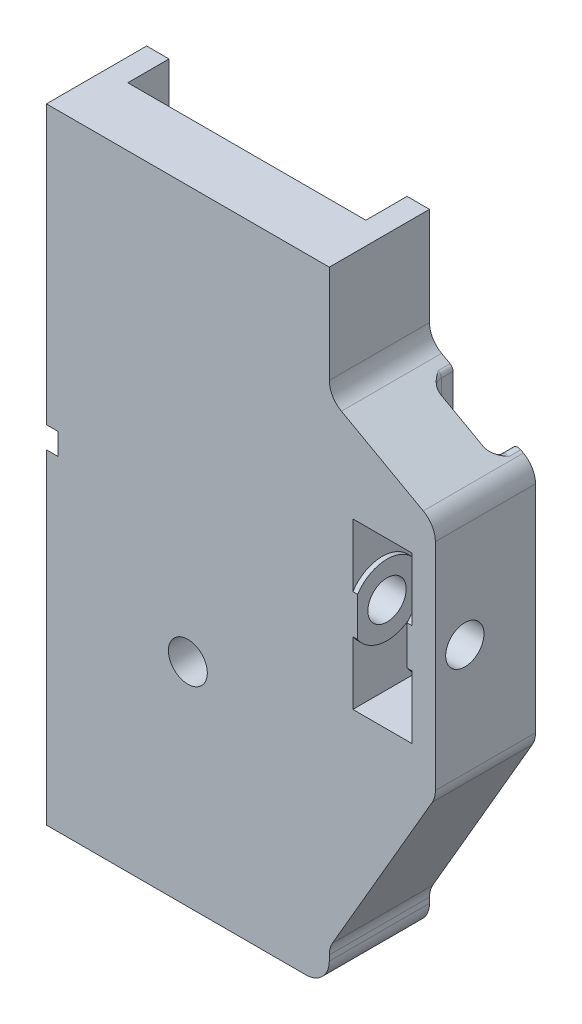
SolidWorks part; units mm, degrees
material "ABS"
ref_plane "前视基准面" through (0, 0, 0) normal (0, 0, 1) x (1, 0, 0)
ref_plane "上视基准面" through (0, 0, 0) normal (0, 1, 0) x (1, 0, 0)
ref_plane "右视基准面" through (0, 0, 0) normal (1, 0, 0) x (0, 0, -1)
other "Configuration Table"
sketch "草图1" plane through (0, 0, 0) normal (0, 0, 1) x (1, 0, 0)
  line L0 (0, 0) -> (0, 53)
  line L1 (0, 53) -> (24, 53)
  line L2 (24, 53) -> (24, 43.5)
  line L3 (24, 43.5) -> (33, 38.5)
  line L4 (33, 38.5) -> (33, 18.5)
  line L5 (33, 18.5) -> (24, 3)
  line L6 (24, 3) -> (24, 0)
  line L7 (24, 0) -> (0, 0)
  line L9 (26, 35.5) -> (31, 35.5)
  line L10 (26, 35.5) -> (26, 21.5)
  line L11 (26, 21.5) -> (31, 21.5)
  line L12 (31, 35.5) -> (31, 21.5)
  circle A0 centre (12, 18) radius 1.65
  dimension "D12" = 3.3
  dimension "D13" = 12
  dimension "D14" = 18
  dimension "D1" = 53
  dimension "D2" = 24
  dimension "D3" = 9
  dimension "D4" = 3
  dimension "D5" = 20
  dimension "D6" = 5
  dimension "D7" = 14.5
  dimension "D8" = 5
  dimension "D9" = 14
  dimension "D10" = 2
  dimension "D11" = 3
extrude "凸台-拉伸1" add sketch "草图1" along normal blind 8.5
sketch "草图2" plane through (0, 53, 0) normal (0, 1, 0) x (1, 0, 0)
  line L0 (24, 0) -> (0, 0) construction
  line L1 (1.9, 0) -> (22.1, 0)
  line L2 (1.9, 0) -> (1.9, -3.5)
  line L3 (1.9, -3.5) -> (22.1, -3.5)
  line L4 (22.1, 0) -> (22.1, -3.5)
  line L5 (0, -8.5) -> (0, 0) construction
  dimension "D1" = 3.5
  dimension "D2" = 1.9
  dimension "D3" = 20.2
extrude "切除-拉伸1" cut sketch "草图2" against normal offset from surface (50.1 mm away) 2.9 up to face at (12, 0, 4.25)
sketch "草图3" plane through (33, 0, 0) normal (1, 0, 0) x (0, 0, -1)
  line L0 (-8.5, 18.5) -> (-8.5, 38.5) construction
  circle A0 centre (-6, 28.5) radius 1.625
  dimension "D1" = 3.25
  dimension "D2" = 2.5
  dimension "D3" = 7
extrude "切除-拉伸2" cut sketch "草图3" against normal up to surface (7 mm away) up to face at (26, 28.5, 4.25)
sketch "草图4" plane through (26, 0, 0) normal (1, 0, 0) x (0, 0, -1)
  circle A0 centre (-6, 28.5) radius 1
  dimension "D1" = 2
extrude "切除-拉伸3" cut sketch "草图4" against normal up to surface (3.9 mm away) up to face at (22.1, 27.95, 1.75)
sketch "草图5" plane through (26, 0, 0) normal (1, 0, 0) x (0, 0, -1)
  line L0 (-8.5, 35.5) -> (-8.5, 21.5) construction
  line L1 (-8.5, 30.1583) -> (-8.5, 26.8417)
  circle A0 centre (-6, 28.5) radius 1 construction
  circle A1 centre (-6, 28.5) radius 1
  arc A2 (-8.5, 26.8417) -> (-8.5, 30.1583) centre (-6, 28.5) ccw
  dimension "D1" = 6
extrude "凸台-拉伸2" add sketch "草图5" along normal blind 0.4
sketch "草图6" plane through (31, 0, 0) normal (-1, 0, 0) x (0, 0, 1)
  line L1 (8.5, 26.8417) -> (8.5, 30.1583)
  line L2 (8.5, 26.8417) -> (8.5, 30.1583)
  circle A0 centre (6, 28.5) radius 1.625 construction
  arc A1 (8.5, 30.1583) -> (8.5, 26.8417) centre (6, 28.5) ccw
  arc A2 (8.5, 30.1583) -> (8.5, 26.8417) centre (6, 28.5) ccw
  circle A3 centre (6, 28.5) radius 1.625
  dimension "D1" = 0
extrude "凸台-拉伸3" add sketch "草图6" along normal blind 0.4
fillet "圆角1" radius 2 1 edges at (24, 3, 4.25)
fillet "圆角2" radius 2 4 edges at (24, 0, 4.25) (33, 18.5, 4.25) (33, 38.5, 4.25) (24, 43.5, 4.25)
sketch "草图7" plane through (33, 0, 0) normal (1, 0, 0) x (0, 0, -1)
  circle A0 centre (-6, 28.5) radius 1.625 construction
  circle A1 centre (-6, 28.5) radius 1.625
extrude "切除-拉伸4" cut sketch "草图7" against normal through all
sketch "草图8" plane through (0, 0, 0) normal (0, 0, -1) x (-1, 0, 0)
  line L0 (-26, 35.5) -> (-26, 21.5) construction
  line L1 (-31, 35.5) -> (-26, 35.5)
  line L2 (-31, 35.5) -> (-31, 44.8225)
  line L3 (-31, 44.8225) -> (-26, 44.8225)
  line L4 (-26, 35.5) -> (-26, 44.8225)
extrude "切除-拉伸5" cut sketch "草图8" against normal blind 2
fillet "圆角3" radius 0.5 2 edges at (31, 39.6111, 1) (26, 42.3889, 1)
fillet "圆角4" radius 1 4 edges at (25.9309, 42.3483, 2) (31.2464, 39.1923, 2) (26, 38.7973, 2) (31, 37.1307, 2)
sketch "Sketch1" plane through (0, 0, 0) normal (-1, 0, 0) x (0, 0, 1)
  line L1 (2.9689, 28.5) -> (4.4845, 25.875)
  line L2 (4.4845, 25.875) -> (7.5155, 25.875)
  line L3 (7.5155, 25.875) -> (9.0311, 28.5)
  line L4 (9.0311, 28.5) -> (7.5155, 31.125)
  line L5 (7.5155, 31.125) -> (4.4845, 31.125)
  line L6 (4.4845, 31.125) -> (2.9689, 28.5)
  circle A0 centre (6, 28.5) radius 2.625 construction
  dimension "D1" = 5.25
extrude "Cut-Extrude1" cut sketch "Sketch1" against normal blind 1
